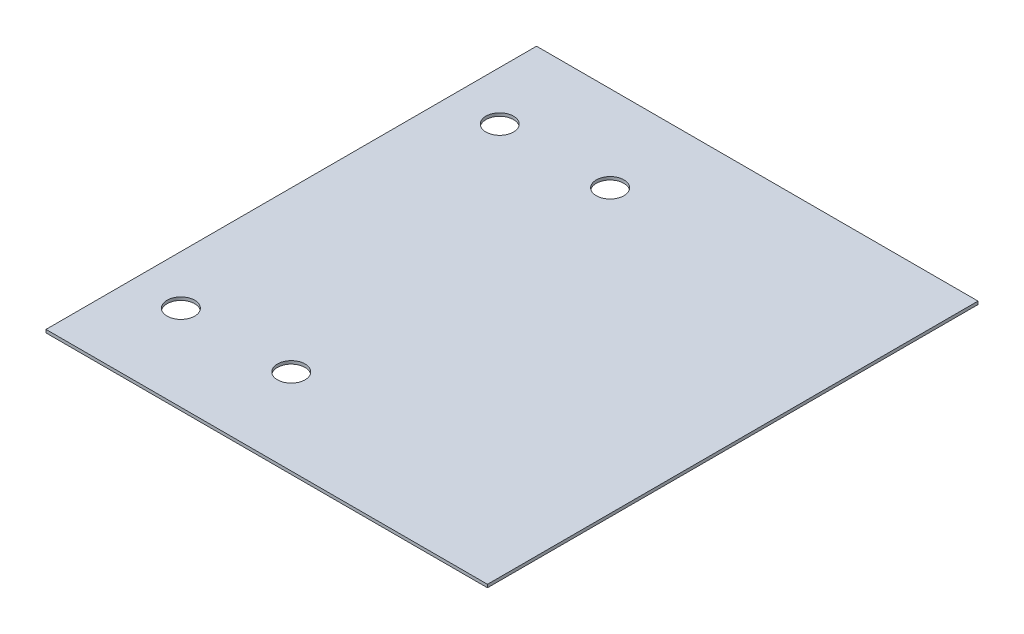
SolidWorks part; units mm, degrees
ref_plane "Front Plane" through (0, 0, 0) normal (0, 0, 1) x (1, 0, 0)
ref_plane "Top Plane" through (0, 0, 0) normal (0, 1, 0) x (1, 0, 0)
ref_plane "Right Plane" through (0, 0, 0) normal (1, 0, 0) x (0, 0, -1)
sketch "Sketch1" plane through (0, 0, 0) normal (0, 1, 0) x (1, 0, 0)
  line L1 (0, 0) -> (457.2, 0)
  line L2 (0, 0) -> (0, 508)
  line L3 (0, 508) -> (457.2, 508)
  line L4 (457.2, 0) -> (457.2, 508)
  dimension "D1" = 457.2
  dimension "D2" = 508
extrude "Boss-Extrude1" add sketch "Sketch1" along normal blind 3.175
sketch "Sketch2" plane through (0, 3.175, 0) normal (0, 1, 0) x (1, 0, 0)
  line L0 (107.95, 419.1) -> (107.95, 508) construction
  line L1 (50.8, 419.1) -> (165.1, 419.1) construction
  line L3 (50.8, 88.9) -> (165.1, 88.9) construction
  line L5 (457.2, 508) -> (0, 508) construction
  line L6 (107.95, 88.9) -> (107.95, 0) construction
  line L7 (0, 0) -> (457.2, 0) construction
  line L9 (0, 508) -> (0, 0) construction
  circle A0 centre (50.8, 419.1) radius 14.2875
  circle A1 centre (165.1, 419.1) radius 14.2875
  circle A2 centre (50.8, 88.9) radius 14.2875
  circle A3 centre (165.1, 88.9) radius 14.2875
  dimension "D1" = 28.575
  dimension "D2" = 28.575
  dimension "D3" = 28.575
  dimension "D4" = 28.575
  dimension "D5" = 114.3
  dimension "D6" = 114.3
  dimension "D7" = 330.2
  dimension "D8" = 50.8
extrude "Cut-Extrude1" cut sketch "Sketch2" against normal blind 3.175
